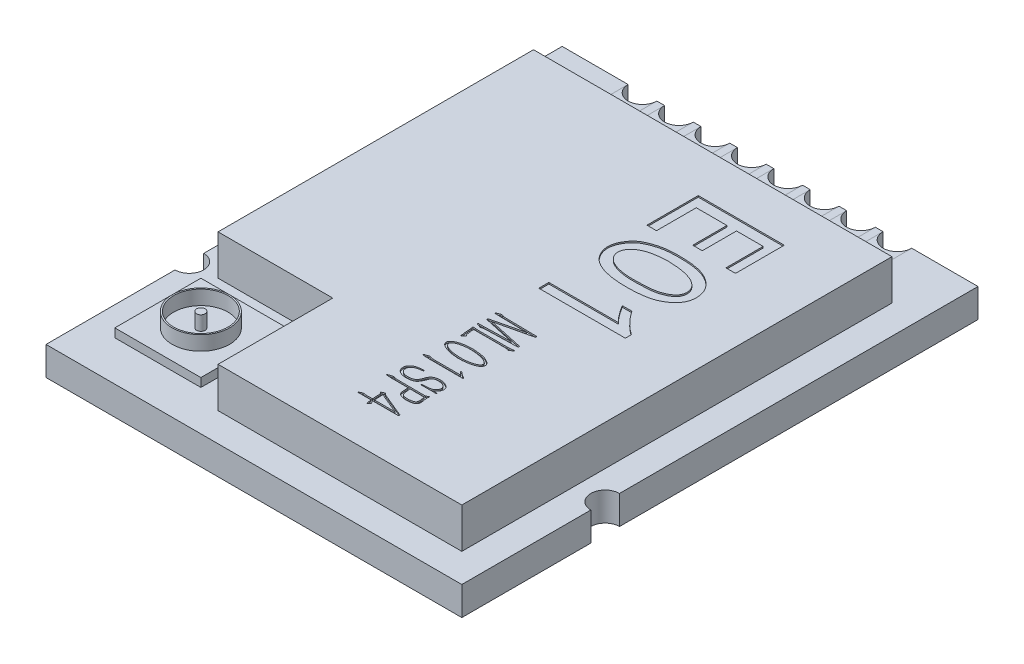
SolidWorks part; units mm, degrees
ref_plane "前视基准面" through (0, 0, 0) normal (0, 0, 1) x (1, 0, 0)
ref_plane "上视基准面" through (0, 0, 0) normal (0, 1, 0) x (1, 0, 0)
ref_plane "右视基准面" through (0, 0, 0) normal (1, 0, 0) x (0, 0, -1)
sketch "草图1" plane through (0, 0, 0) normal (0, 1, 0) x (1, 0, 0)
  line L0 (0, 40.9442) -> (0, -39.2925) construction
  line L1 (-7.25, 9) -> (7.25, 9)
  line L2 (-7.25, 9) -> (-7.25, -9)
  line L3 (-7.25, -9) -> (7.25, -9)
  line L4 (7.25, 9) -> (7.25, -9)
  line L5 (-49.0501, 0) -> (55.3021, 0) construction
  dimension "D1" = 18
  dimension "D2" = 14.5
extrude "凸台-拉伸1" add sketch "草图1" along normal blind 1
sketch "草图2" plane through (0, 1, 0) normal (0, 1, 0) x (1, 0, 0)
  line L0 (-6.25, 7) -> (6.25, 7)
  line L1 (6.25, 7) -> (6.25, -8)
  line L2 (6.25, -8) -> (-2.25, -8)
  line L3 (-2.25, -8) -> (-2.25, -4)
  line L4 (-2.25, -4) -> (-6.25, -4)
  line L5 (-6.25, -4) -> (-6.25, 7)
  line L6 (7.25, -9) -> (7.25, 9) construction
  line L7 (-7.25, 9) -> (-7.25, -9) construction
  line L8 (-7.25, -9) -> (7.25, -9) construction
  line L9 (7.25, 9) -> (-7.25, 9) construction
  dimension "D1" = 1
  dimension "D2" = 1
  dimension "D3" = 1
  dimension "D4" = 2
  dimension "D5" = 4
extrude "凸台-拉伸2" add sketch "草图2" along normal blind 1.4
sketch "草图3" plane through (0, 1, 0) normal (0, 1, 0) x (1, 0, 0)
  line L0 (-6.25, -4) -> (-2.25, -4) construction
  line L1 (-6.25, -4.6) -> (-3.25, -4.6)
  line L2 (-6.25, -4.6) -> (-6.25, -7.6)
  line L3 (-6.25, -7.6) -> (-3.25, -7.6)
  line L4 (-3.25, -4.6) -> (-3.25, -7.6)
  line L5 (-2.25, -4) -> (-2.25, -8) construction
  dimension "D1" = 3
  dimension "D2" = 0.6
  dimension "D3" = 1
extrude "凸台-拉伸3" add sketch "草图3" along normal blind 0.3
sketch "草图4" plane through (0, 1.3, 0) normal (0, 1, 0) x (1, 0, 0)
  line L0 (-6.25, -6.1) -> (-3.25, -6.1) construction
  line L1 (-6.25, -4.6) -> (-6.25, -7.6) construction
  line L2 (-3.25, -7.6) -> (-3.25, -4.6) construction
  line L3 (-4.75, -4.6) -> (-4.75, -7.6) construction
  line L4 (-3.25, -4.6) -> (-6.25, -4.6) construction
  line L5 (-6.25, -7.6) -> (-3.25, -7.6) construction
  circle A0 centre (-4.75, -6.1) radius 0.15
  circle A1 centre (-4.75, -6.1) radius 1
  circle A2 centre (-4.75, -6.1) radius 0.95
  dimension "D1" = 0.3
  dimension "D2" = 1.9
  dimension "D3" = 2
extrude "凸台-拉伸4" add sketch "草图4" along normal blind 0.5 contours A1 A2 | A0 region at (-4.75, 1.3, 6.1) region at (-5.7217, 1.3, 6.1)
sketch "草图5" plane through (0, 1, 0) normal (0, 1, 0) x (1, 0, 0)
  line L0 (7.25, 9) -> (-7.25, 9) construction
  line L1 (-7.25, 9) -> (-7.25, -9) construction
  line L2 (7.25, -9) -> (7.25, 9) construction
  line L3 (-4.95, 9) -> (-4.95, 7.8)
  line L4 (-4.95, 7.8) -> (-3.95, 7.8)
  line L5 (-3.95, 7.8) -> (-3.95, 9)
  line L6 (-2.68, 7.8) -> (-2.68, 9)
  line L7 (-3.68, 7.8) -> (-2.68, 7.8)
  line L8 (-3.68, 9) -> (-3.68, 7.8)
  line L9 (-1.41, 7.8) -> (-1.41, 9)
  line L10 (-2.41, 7.8) -> (-1.41, 7.8)
  line L11 (-2.41, 9) -> (-2.41, 7.8)
  line L12 (-0.14, 7.8) -> (-0.14, 9)
  line L13 (-1.14, 7.8) -> (-0.14, 7.8)
  line L14 (-1.14, 9) -> (-1.14, 7.8)
  line L15 (1.13, 7.8) -> (1.13, 9)
  line L16 (0.13, 7.8) -> (1.13, 7.8)
  line L17 (0.13, 9) -> (0.13, 7.8)
  line L18 (2.4, 7.8) -> (2.4, 9)
  line L19 (1.4, 7.8) -> (2.4, 7.8)
  line L20 (1.4, 9) -> (1.4, 7.8)
  line L21 (3.67, 7.8) -> (3.67, 9)
  line L22 (2.67, 7.8) -> (3.67, 7.8)
  line L23 (2.67, 9) -> (2.67, 7.8)
  line L24 (4.94, 7.8) -> (4.94, 9)
  line L25 (3.94, 7.8) -> (4.94, 7.8)
  line L26 (3.94, 9) -> (3.94, 7.8)
  circle A0 centre (-4.45, 9) radius 0.5
  circle A1 centre (-3.18, 9) radius 0.5
  circle A2 centre (-1.91, 9) radius 0.5
  circle A3 centre (-0.64, 9) radius 0.5
  circle A4 centre (0.63, 9) radius 0.5
  circle A5 centre (1.9, 9) radius 0.5
  circle A6 centre (3.17, 9) radius 0.5
  circle A7 centre (4.44, 9) radius 0.5
  circle A8 centre (-7.25, -4) radius 0.5
  circle A9 centre (7.25, -4) radius 0.5
  line M15 (-7.25, 9) -> (-7.25, -9)
  line M17 (7.25, -9) -> (7.25, 9)
  line M18 (7.25, 9) -> (-7.25, 9)
  dimension "D1" = 1
  dimension "D5" = 1
  dimension "D2" = 2.8
  dimension "D4" = 1.27
  dimension "D6" = 13
  dimension "D8" = 1.2
  dimension "D7" = 2
  dimension "D3" = 8
extrude "切除-拉伸2" cut sketch "草图5" against normal blind 1 contours A0 M18 | A1 M18 | A2 M18 | A3 M18 | A4 M18 | A5 M18 | A6 M18 | A7 M18 | A8 M15 | A9 M17 region at (7.0378, 1, 4) region at (4.44, 1, -8.7878) region at (3.17, 1, -8.7878) region at (1.9, 1, -8.7878) region at (0.63, 1, -8.7878) region at (-0.64, 1, -8.7878) region at (-1.91, 1, -8.7878) region at (-3.18, 1, -8.7878) region at (-4.45, 1, -8.7878) region at (-7.0378, 1, 4)
split line "分割线2"
sketch "草图5<4>" plane through (0, 1, 0) normal (0, 1, 0) x (1, 0, 0) same geometry as "草图5"
sketch "草图8" plane through (0, 2.4, 0) normal (0, 1, 0) x (1, 0, 0)
  line L0 (0.939, 5.7142) -> (0.939, 0.3284) construction
  line L1 (0.939, -1.5246) -> (0.939, -7.4637) construction
  text T0 "E01" font "黑体" height 3
  text T1 "ML01SP4" font "汉仪长仿宋体" height 1.5
extrude "切除-拉伸3" cut sketch "草图8" against normal blind 0.05
